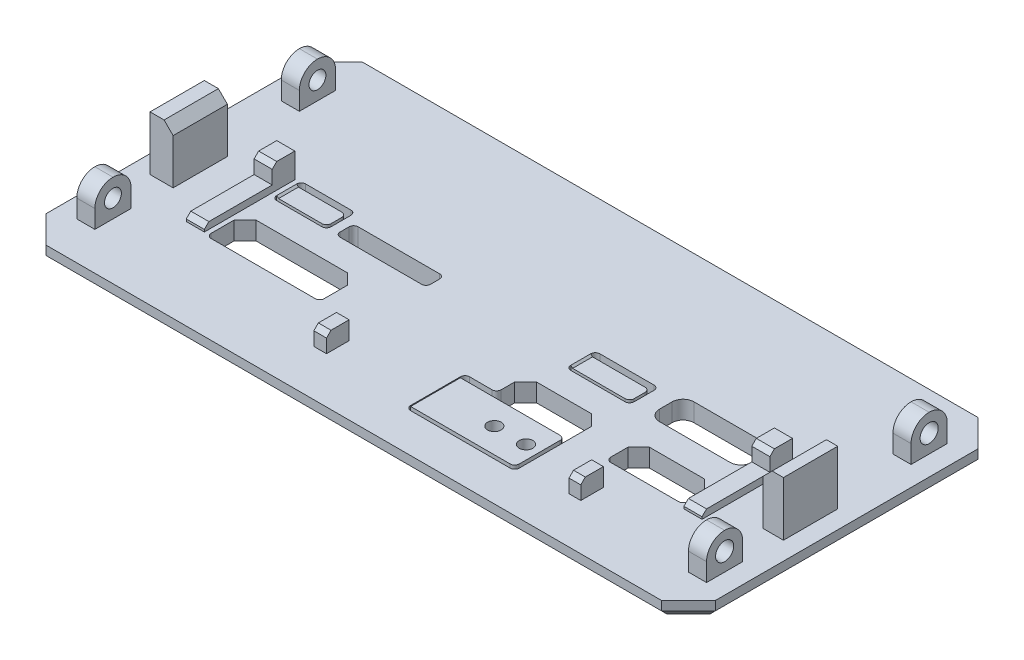
SolidWorks part; units mm, degrees
ref_plane "前视基准面" through (0, 0, 0) normal (0, 0, 1) x (1, 0, 0)
ref_plane "上视基准面" through (0, 0, 0) normal (0, 1, 0) x (1, 0, 0)
ref_plane "右视基准面" through (0, 0, 0) normal (1, 0, 0) x (0, 0, -1)
other "Configuration Table"
sketch "草图2" plane through (0, 0, 0) normal (0, 1, 0) x (1, 0, 0)
  line L0 (-36.7624, 30.764) -> (-33.7624, 33.764)
  line L1 (-36.7624, 1.764) -> (-33.7624, -1.236)
  line L2 (-33.7624, 33.764) -> (34.2376, 33.764)
  line L3 (-36.7624, 30.764) -> (-36.7624, 1.764)
  line L4 (-33.7624, -1.236) -> (34.2376, -1.236)
  line L5 (37.2376, 30.764) -> (37.2376, 1.764)
  line L6 (34.2376, -1.236) -> (37.2376, 1.764)
  line L7 (34.2376, 33.764) -> (37.2376, 30.764)
  point P5 (-36.7624, -1.236)
  point P7 (-36.7624, -1.236)
  point P8 (37.2376, 33.764)
  point P10 (37.2376, 33.764)
  point P11 (37.2376, -1.236)
  point P13 (-36.7624, 33.764)
  point P15 (-36.7624, 33.764)
  dimension "D1" = 74
  dimension "D2" = 35
extrude "凸台-拉伸1" add sketch "草图2" along normal blind 2
chamfer "倒角1" distance 1 angle 45 8 edges at (-36.7624, 0, -16.264) (0.2376, 0, -33.764) (0.2376, 0, 1.236) (37.2376, 0, -16.264) (-35.2624, 0, -32.264) (-35.2624, 0, -0.264) (35.7376, 0, -0.264) (35.7376, 0, -32.264)
sketch "草图3" plane through (0, 0, 0) normal (0, -1, 0) x (1, 0, 0)
  line L1 (-25.7624, -8.514) -> (-13.2624, -8.514)
  line L2 (-25.7624, -8.514) -> (-25.7624, -12.764)
  line L3 (-25.7624, -12.764) -> (-13.2624, -12.764)
  line L4 (-13.2624, -8.514) -> (-13.2624, -12.764)
  line L5 (1.7376, -3.064) -> (13.7376, -3.064)
  line L7 (5.2376, -12.764) -> (13.7376, -12.764)
  line L8 (13.7376, -3.064) -> (13.7376, -12.764)
  line L9 (17.7376, -9.164) -> (26.2376, -9.164)
  line L10 (17.7376, -9.164) -> (17.7376, -12.764)
  line L11 (17.7376, -12.764) -> (26.2376, -12.764)
  line L12 (26.2376, -9.164) -> (26.2376, -12.764)
  line L13 (15.8376, -15.764) -> (26.0376, -15.764)
  line L14 (15.8376, -15.764) -> (15.8376, -19.564)
  line L15 (15.8376, -19.564) -> (26.0376, -19.564)
  line L16 (26.0376, -15.764) -> (26.0376, -19.564)
  line L17 (6.7376, -15.764) -> (13.7376, -15.764)
  line L18 (6.7376, -15.764) -> (6.7376, -18.964)
  line L19 (6.7376, -18.964) -> (13.7376, -18.964)
  line L20 (13.7376, -15.764) -> (13.7376, -18.964)
  line L21 (-25.7624, -15.764) -> (-19.7624, -15.764)
  line L22 (-25.7624, -15.764) -> (-25.7624, -18.964)
  line L23 (-25.7624, -18.964) -> (-19.7624, -18.964)
  line L24 (-19.7624, -15.764) -> (-19.7624, -18.964)
  line L25 (-18.7624, -15.764) -> (-8.7624, -15.764)
  line L26 (-18.7624, -15.764) -> (-18.7624, -17.764)
  line L27 (-18.7624, -17.764) -> (-8.7624, -17.764)
  line L28 (-8.7624, -15.764) -> (-8.7624, -17.764)
  line L29 (-36.7624, -30.764) -> (-36.7624, -1.764) construction
  line L30 (-34.7624, -15.764) -> (-43.2418, -15.764) construction
  line L31 (37.2376, -1.764) -> (37.2376, -30.764) construction
  line L32 (-35.2588, -12.764) -> (-41.1207, -12.764) construction
  line L33 (-33.7624, 1.236) -> (34.2376, 1.236) construction
  line L34 (34.2376, -33.764) -> (-33.7624, -33.764) construction
  line L35 (5.2376, -12.764) -> (5.2376, -9.564)
  line L36 (5.2376, -9.564) -> (1.7376, -9.564)
  line L37 (1.7376, -9.564) -> (1.7376, -3.064)
  dimension "D1" = 14
  dimension "D2" = 18
  dimension "D3" = 12.5
  dimension "D4" = 4.25
  dimension "D5" = 3.2
  dimension "D6" = 2
  dimension "D7" = 6
  dimension "D8" = 11
  dimension "D9" = 1
  dimension "D10" = 10
  dimension "D11" = 23.5
  dimension "D12" = 7
  dimension "D13" = 3.8
  dimension "D14" = 3.6
  dimension "D15" = 11
  dimension "D16" = 11.2
  dimension "D17" = 10.2
  dimension "D18" = 8.5
  dimension "D19" = 12
  dimension "D20" = 6.5
  dimension "D21" = 8.5
  dimension "D22" = 3.2
extrude "切除-拉伸1" cut sketch "草图3" against normal up to next
fillet "圆角1" radius 1.2 4 edges at (26.0376, 1, -15.764) (26.0376, 1, -19.564) (15.8376, 1, -19.564) (15.8376, 1, -15.764)
fillet "圆角2" radius 0.5 20 edges at (-8.7624, 1, -15.764) (-8.7624, 1, -17.764) (-18.7624, 1, -17.764) (-18.7624, 1, -15.764) (-19.7624, 1, -18.964) (-19.7624, 1, -15.764) (-25.7624, 1, -18.964) (-25.7624, 1, -15.764) (6.7376, 1, -18.964) (13.7376, 1, -18.964) (13.7376, 1, -15.764) (6.7376, 1, -15.764) (13.7376, 1, -3.064) (17.7376, 1, -9.164) (26.2376, 1, -9.164) (-13.2624, 1, -8.514) (-25.7624, 1, -8.514) (1.7376, 1, -3.064) (1.7376, 1, -9.564) (5.2376, 1, -9.564)
chamfer "倒角2" distance 1.2 angle 45 6 edges at (26.2376, 1, -12.764) (17.7376, 1, -12.764) (13.7376, 1, -12.764) (-13.2624, 1, -12.764) (-25.7624, 1, -12.764) (5.2376, 1, -12.764)
sketch "草图4" plane through (0, 0, 0) normal (0, -1, 0) x (1, 0, 0)
  line L0 (13.2376, -3.064) -> (2.2376, -3.064) construction
  line L1 (-23.7624, -16.264) -> (-20.2624, -16.264)
  line L2 (-23.7624, -16.264) -> (-23.7624, -18.464)
  line L3 (-23.7624, -18.464) -> (-20.2624, -18.464)
  line L4 (-20.2624, -16.264) -> (-20.2624, -18.464)
  line L5 (6.7376, -3.564) -> (13.2376, -3.564)
  line L6 (6.7376, -3.564) -> (6.7376, -9.064)
  line L7 (6.7376, -9.064) -> (13.2376, -9.064)
  line L8 (13.2376, -3.564) -> (13.2376, -9.064)
  line L9 (8.7376, -16.264) -> (13.2376, -16.264)
  line L10 (8.7376, -16.264) -> (8.7376, -18.464)
  line L11 (8.7376, -18.464) -> (13.2376, -18.464)
  line L12 (13.2376, -16.264) -> (13.2376, -18.464)
  line L13 (13.7376, -11.564) -> (13.7376, -3.564) construction
  line L15 (2.2376, -9.564) -> (4.7376, -9.564) construction
  line L16 (13.7376, -18.464) -> (13.7376, -16.264) construction
  line L17 (7.2376, -18.964) -> (13.2376, -18.964) construction
  line L18 (13.2376, -15.764) -> (7.2376, -15.764) construction
  line L19 (-20.2624, -15.764) -> (-25.2624, -15.764) construction
  line L20 (-25.2624, -18.964) -> (-20.2624, -18.964) construction
  line L21 (-19.7624, -18.464) -> (-19.7624, -16.264) construction
  dimension "D1" = 0.5
  dimension "D2" = 6.5
  dimension "0.5" = 0.5
  dimension "D3" = 0.5
  dimension "D4" = 0.5
  dimension "D5" = 0.5
  dimension "D6" = 0.5
  dimension "D7" = 4.5
  dimension "D8" = 0.5
  dimension "D9" = 0.5
  dimension "D10" = 0.5
  dimension "D11" = 3.5
extrude "凸台-拉伸2" add sketch "草图4" against normal blind 1 separate body
sketch "草图5" plane through (0, 1, 0) normal (0, 1, 0) x (1, 0, 0)
  line L0 (-25.7624, 18.464) -> (-25.7624, 16.264) construction
  line L1 (-20.2624, 16.264) -> (-25.7624, 16.264)
  line L2 (-20.2624, 16.264) -> (-20.2624, 18.464)
  line L3 (-20.2624, 18.464) -> (-25.7624, 18.464)
  line L4 (-25.7624, 16.264) -> (-25.7624, 18.464)
  line L5 (8.7376, 18.464) -> (13.2376, 18.464) construction
  line L6 (13.2376, 16.264) -> (6.7376, 16.264)
  line L7 (13.2376, 16.264) -> (13.2376, 18.464)
  line L8 (13.2376, 18.464) -> (6.7376, 18.464)
  line L9 (6.7376, 16.264) -> (6.7376, 18.464)
extrude "凸台-拉伸3" add sketch "草图5" along normal blind 0.8
sketch "草图6" plane through (0, 1, 0) normal (0, 1, 0) x (1, 0, 0)
  line L2 (13.2376, 3.564) -> (1.7376, 3.564)
  line L3 (13.2376, 3.564) -> (13.2376, 9.064)
  line L4 (13.2376, 9.064) -> (1.7376, 9.064)
  line L5 (1.7376, 3.564) -> (1.7376, 9.064)
extrude "凸台-拉伸4" add sketch "草图6" along normal blind 0.9
fillet "圆角5" radius 1 3 edges at (6.7376, 1, -17.364) (-25.7624, 1, -17.364) (1.7376, 1, -6.314)
fillet "圆角3" radius 0.5 12 edges at (8.7376, 0.5, -16.264) (8.7376, 0.5, -18.464) (13.2376, 0.9, -18.464) (13.2376, 0.9, -16.264) (-20.2624, 0.9, -16.264) (-20.2624, 0.9, -18.464) (-23.7624, 0.5, -18.464) (-23.7624, 0.5, -16.264) (13.2376, 0.95, -3.564) (6.7376, 0.5, -3.564) (13.2376, 0.95, -9.064) (6.7376, 0.5, -9.064)
chamfer "倒角3" distance 0.2 angle 45 2 edges at (-25.7624, 1.8, -17.364) (6.7376, 1.8, -17.364)
sketch "草图7" plane through (0, 2, 0) normal (0, 1, 0) x (1, 0, 0)
  line L0 (34.2376, -1.236) -> (-33.7624, -1.236) construction
  line L1 (-7.8624, 6.364) -> (-9.2624, 6.364)
  line L2 (-7.8624, 6.364) -> (-7.8624, 3.864)
  line L3 (-7.8624, 3.864) -> (-9.2624, 3.864)
  line L4 (-9.2624, 6.364) -> (-9.2624, 3.864)
  line L5 (20.2376, 3.864) -> (18.9376, 3.864)
  line L6 (20.2376, 3.864) -> (20.2376, 6.364)
  line L7 (20.2376, 6.364) -> (18.9376, 6.364)
  line L8 (18.9376, 3.864) -> (18.9376, 6.364)
  line L9 (37.2376, 1.764) -> (37.2376, 30.764) construction
  line L10 (-36.7624, 1.764) -> (-36.7624, 30.764) construction
  dimension "D1" = 5.1
  dimension "D2" = 17
  dimension "D3" = 27.5
  dimension "D4" = 1.3
  dimension "D5" = 1.4
  dimension "D6" = 2.5
extrude "凸台-拉伸5" add sketch "草图7" along normal blind 2
sketch "草图11" plane through (0, 2, 0) normal (0, 1, 0) x (1, 0, 0)
  line L0 (-33.7624, -1.236) -> (34.2376, -1.236) construction
  line L1 (28.7376, 8.764) -> (26.7376, 8.764)
  line L2 (28.7376, 8.764) -> (28.7376, 18.764)
  line L3 (28.7376, 18.764) -> (26.7376, 18.764)
  line L4 (26.7376, 8.764) -> (26.7376, 18.764)
  line L5 (-26.2624, 8.764) -> (-28.2624, 8.764)
  line L6 (-26.2624, 8.764) -> (-26.2624, 18.764)
  line L7 (-26.2624, 18.764) -> (-28.2624, 18.764)
  line L8 (-28.2624, 8.764) -> (-28.2624, 18.764)
  line L9 (-36.7624, 30.764) -> (-36.7624, 1.764) construction
  line L10 (37.2376, 1.764) -> (37.2376, 30.764) construction
  dimension "D1" = 10
  dimension "D2" = 8.5
  dimension "D3" = 2
  dimension "D4" = 10
  dimension "D5" = 8.5
  dimension "D6" = 2
extrude "凸台-拉伸7" add sketch "草图11" along normal blind 0.75
sketch "草图12" plane through (0, 2.75, 0) normal (0, 1, 0) x (1, 0, 0)
  line L0 (26.7376, 18.764) -> (26.7376, 8.764) construction
  line L1 (28.7376, 18.764) -> (26.7376, 18.764)
  line L2 (28.7376, 18.764) -> (28.7376, 16.264)
  line L3 (28.7376, 16.264) -> (26.7376, 16.264)
  line L4 (26.7376, 18.764) -> (26.7376, 16.264)
  line L5 (-28.2624, 18.764) -> (-28.2624, 8.764) construction
  line L6 (-26.2624, 18.764) -> (-28.2624, 18.764)
  line L7 (-26.2624, 18.764) -> (-26.2624, 16.264)
  line L8 (-26.2624, 16.264) -> (-28.2624, 16.264)
  line L9 (-28.2624, 18.764) -> (-28.2624, 16.264)
  dimension "D1" = 2.5
extrude "凸台-拉伸8" add sketch "草图12" along normal blind 2
chamfer "倒角4" distance 0.5 angle 45 6 edges at (-8.5624, 4, -3.864) (19.5876, 4, -3.864) (-27.2624, 2.75, -8.764) (27.7376, 2.75, -8.764) (-27.2624, 4.75, -16.264) (27.7376, 4.75, -16.264)
sketch "草图8" plane through (0, 2, 0) normal (0, 1, 0) x (1, 0, 0)
  line L1 (35.0376, 2.964) -> (33.0376, 2.964)
  line L2 (35.0376, 2.964) -> (35.0376, 6.964)
  line L3 (35.0376, 6.964) -> (33.0376, 6.964)
  line L4 (33.0376, 2.964) -> (33.0376, 6.964)
  line L6 (35.0376, 25.564) -> (33.0376, 25.564)
  line L7 (35.0376, 25.564) -> (35.0376, 29.564)
  line L8 (35.0376, 29.564) -> (33.0376, 29.564)
  line L9 (33.0376, 25.564) -> (33.0376, 29.564)
  line L10 (-34.5624, 2.964) -> (-32.5624, 2.964)
  line L11 (-34.5624, 2.964) -> (-34.5624, 6.964)
  line L12 (-34.5624, 6.964) -> (-32.5624, 6.964)
  line L13 (-32.5624, 2.964) -> (-32.5624, 6.964)
  line L15 (-34.5624, 25.564) -> (-32.5624, 25.564)
  line L16 (-34.5624, 25.564) -> (-34.5624, 29.564)
  line L17 (-34.5624, 29.564) -> (-32.5624, 29.564)
  line L18 (-32.5624, 25.564) -> (-32.5624, 29.564)
  line L21 (-36.7624, 30.764) -> (-36.7624, 1.764) construction
  line L22 (34.2376, 33.764) -> (-33.7624, 33.764) construction
  line L23 (-33.7624, -1.236) -> (34.2376, -1.236) construction
  line L24 (37.2376, 1.764) -> (37.2376, 30.764) construction
  point P4 (0, 0)
  point P5 (0, 0)
  point P20 (0, 0)
  point P22 (0, 0)
  point P24 (0, 0)
  point P26 (0, 0)
  point P27 (0, 0)
  point P29 (0, 0)
  point P30 (0, 0)
  point P31 (0, 0)
  point P32 (0, 0)
  point P33 (0, 0)
  point P38 (0, 0)
  point P39 (0, 0)
  point P40 (0, 0)
  point P41 (0, 0)
  point P44 (0, 0)
  dimension "D1" = 4
  dimension "D2" = 2.2
  dimension "D3" = 4.2
  dimension "D4" = 4.2
  dimension "D5" = 2.2
  dimension "D6" = 2
extrude "凸台-拉伸6" add sketch "草图8" along normal blind 4
fillet "圆角4" radius 2 8 edges at (34.0376, 6, -6.964) (34.0376, 6, -2.964) (34.0376, 6, -29.564) (34.0376, 6, -25.564) (-33.5624, 6, -25.564) (-33.5624, 6, -29.564) (-33.5624, 6, -2.964) (-33.5624, 6, -6.964)
sketch "草图9" plane through (-34.5624, 0, 0) normal (-1, 0, 0) x (0, 0, 1)
  circle A0 centre (-4.964, 4) radius 1
  circle A1 centre (-27.564, 4) radius 1
  dimension "D1" = 2
extrude "切除-拉伸2" cut sketch "草图9" against normal up to next (2 mm away) draft 2
sketch "草图10" plane through (35.0376, 0, 0) normal (1, 0, 0) x (0, 0, -1)
  circle A0 centre (4.964, 4) radius 1
  circle A1 centre (27.564, 4) radius 1
  dimension "D1" = 2
extrude "切除-拉伸3" cut sketch "草图10" against normal up to next (2 mm away) draft 2
sketch "草图13" plane through (0, 2, 0) normal (0, 1, 0) x (1, 0, 0)
  line L0 (35.2376, 29.9355) -> (35.2376, 2.5924) construction
  line L1 (35.2376, 11.264) -> (32.9876, 11.264)
  line L2 (35.2376, 11.264) -> (35.2376, 17.264)
  line L3 (35.2376, 17.264) -> (32.9876, 17.264)
  line L4 (32.9876, 11.264) -> (32.9876, 17.264)
  line L5 (-34.7624, 2.5924) -> (-34.7624, 29.9355) construction
  line L6 (-34.7624, 11.264) -> (-32.2124, 11.264)
  line L7 (-34.7624, 11.264) -> (-34.7624, 17.264)
  line L8 (-34.7624, 17.264) -> (-32.2124, 17.264)
  line L9 (-32.2124, 11.264) -> (-32.2124, 17.264)
  line L10 (34.2376, -1.236) -> (-33.7624, -1.236) construction
  dimension "D1" = 12.5
  dimension "D2" = 6
  dimension "D3" = 2.25
  dimension "D4" = 2.55
extrude "凸台-拉伸9" add sketch "草图13" along normal blind 6
chamfer "倒角5" distance 1 angle 45 2 edges at (-32.2124, 8, -14.264) (32.9876, 8, -14.264)
sketch "草图14" plane through (0, 0, 0) normal (0, -1, 0) x (1, 0, 0)
  line L0 (7.0755, -6.314) -> (5.3752, -6.314) construction
  line L3 (13.2376, -8.564) -> (13.2376, -4.064) construction
  circle A0 centre (11.7376, -6.314) radius 0.75
  circle A1 centre (8.2376, -6.314) radius 0.75
  point P5 (13.2376, -6.314)
  dimension "D1" = 1.5
  dimension "D2" = 3.5
  dimension "D3" = 1.5
extrude "切除-拉伸4" cut sketch "草图14" against normal up to next
